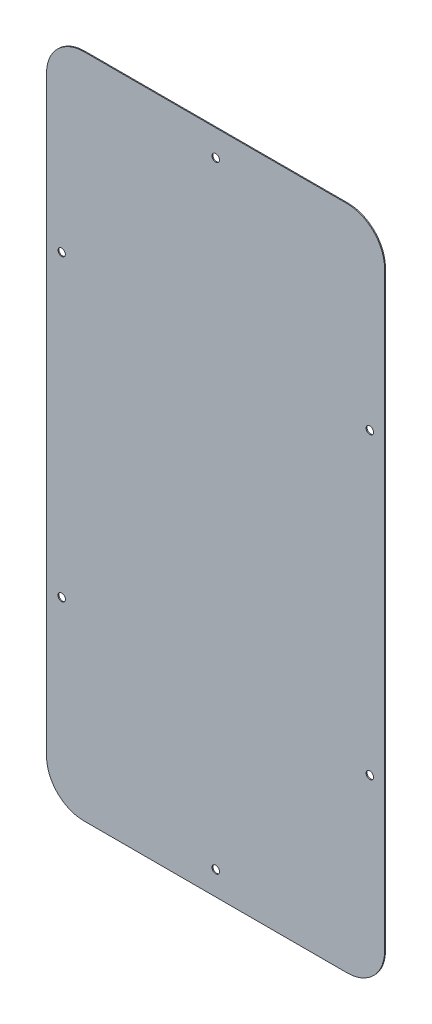
SolidWorks part; units mm, degrees
material "AISI 316 Нержавеющая сталь, лист (SS)"
ref_plane "Спереди" through (0, 0, 0) normal (0, 0, 1) x (1, 0, 0)
ref_plane "Сверху" through (0, 0, 0) normal (0, 1, 0) x (1, 0, 0)
ref_plane "Справа" through (0, 0, 0) normal (1, 0, 0) x (0, 0, -1)
sketch "Эскиз1" plane through (0, 0, 0) normal (0, 0, 1) x (1, 0, 0)
  line L0 (85.5687, 21.1894) -> (85.5687, 37.5182) construction
  line L1 (15.0687, 21.1894) -> (156.0687, 21.1894)
  line L2 (-4.9313, 1.1894) -> (-4.9313, -315.5717)
  line L3 (15.0687, -335.5717) -> (156.0687, -335.5717)
  line L4 (176.0687, 1.1894) -> (176.0687, -315.5717)
  arc A0 (15.0687, 21.1894) -> (-4.9313, 1.1894) centre (15.0687, 1.1894) ccw
  arc A1 (176.0687, 1.1894) -> (156.0687, 21.1894) centre (156.0687, 1.1894) ccw
  arc A2 (156.0687, -335.5717) -> (176.0687, -315.5717) centre (156.0687, -315.5717) ccw
  arc A3 (-4.9313, -315.5717) -> (15.0687, -335.5717) centre (15.0687, -315.5717) ccw
  dimension "D1" = 20
extrude "Вытянуть1" add sketch "Эскиз1" along normal blind 0.5
sketch "Sketch1" plane through (0, 0, 0.5) normal (0, 0, 1) x (1, 0, 0)
  line L1 (156.0687, 21.1894) -> (15.0687, 21.1894) construction
  circle A0 centre (85.6739, 7.1894) radius 2
  circle A1 centre (85.6739, -322.8106) radius 2
  circle A2 centre (3.1739, -237.8106) radius 2
  circle A3 centre (3.1739, -77.8106) radius 1.9508
  circle A4 centre (168.1739, -77.8106) radius 2
  circle A5 centre (168.1739, -237.8106) radius 2
  dimension "D1" = 14
extrude "Cut-Extrude1" cut sketch "Sketch1" against normal through all
